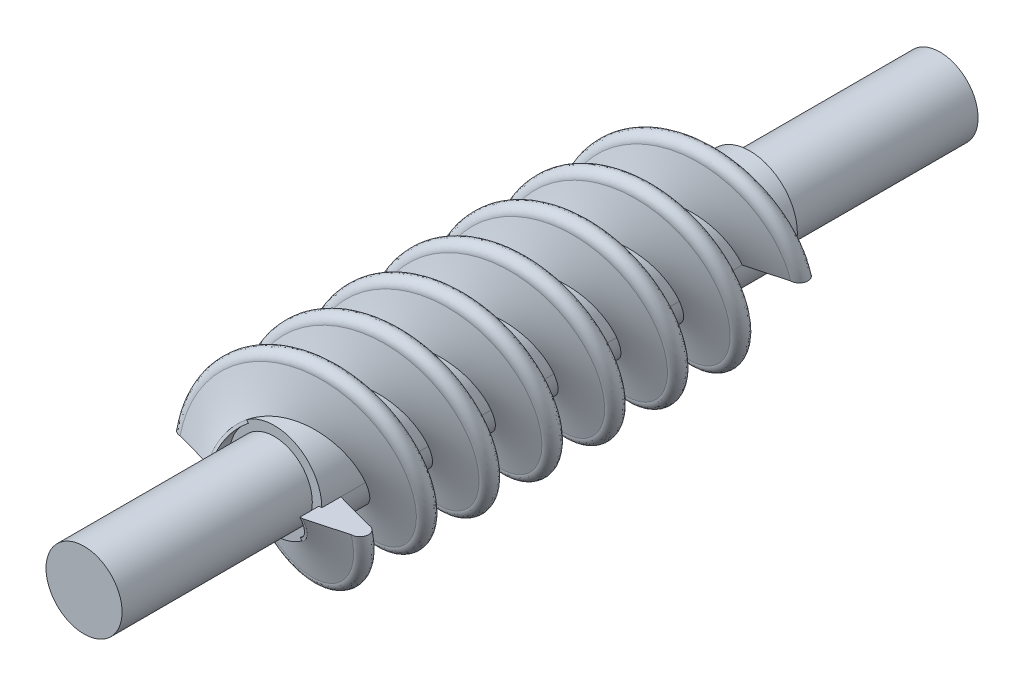
SolidWorks part; units mm, degrees
ref_plane "Plan de face" through (0, 0, 0) normal (0, 0, 1) x (1, 0, 0)
ref_plane "Plan de dessus" through (0, 0, 0) normal (0, 1, 0) x (1, 0, 0)
ref_plane "Plan de droite" through (0, 0, 0) normal (1, 0, 0) x (0, 0, -1)
sketch "Esquisse1" plane through (0, 0, 0) normal (0, 0, 1) x (1, 0, 0)
  circle A0 centre (0, 0) radius 5
  dimension "D1" = 10
extrude "Boss.-Extru.1" add sketch "Esquisse1" along normal blind 50
sketch "Esquisse3" plane through (0, 0, 50) normal (0, 0, 1) x (1, 0, 0)
  circle A0 centre (0, 0) radius 5
curve "Hélice/Spirale1" pitch 13.2 height 46.2 radius 5 centre (0, 0, 50) axis (0, 0, -1) start towards (-1, 0, 0)
sketch "Esquisse4" plane through (0, 0, 0) normal (0, 1, 0) x (1, 0, 0)
  line L0 (-5, -50) -> (-9, -50) construction
  line L1 (-5, 0) -> (-5, -50) construction
  line L2 (-9, -49.1) -> (-5, -48)
  line L3 (-9, -50.9) -> (-5, -52)
  line L5 (-5, -48) -> (-4.702, -48)
  line L6 (-4.702, -48) -> (-4.702, -52)
  line L7 (-4.702, -52) -> (-5, -52)
  arc A1 (-9, -49.1) -> (-9, -50.9) centre (-9, -50) ccw
  spline S0 degree 3 poles (-5, -50) (-5, -49.7265) (-4.7397, -49.1743) (-3.6276, -48.3502) (-1.9632, -47.525) (0, -46.7) (1.9632, -45.875) (3.6276, -45.05) (4.7397, -44.225) (5.1302, -43.4) (4.7397, -42.575) (3.6276, -41.75) (1.4084, -40.65) (-1.4084, -39.55) (-3.6276, -38.45) (-4.7397, -37.625) (-5.1302, -36.8) (-4.7397, -35.975) (-3.6276, -35.15) (-1.4084, -34.05) (1.4084, -32.95) (3.6276, -31.85) (4.7397, -31.025) (5.1302, -30.2) (4.7397, -29.375) (3.6276, -28.55) (1.4084, -27.45) (-1.4084, -26.35) (-3.6276, -25.25) (-4.7397, -24.425) (-5.1302, -23.6) (-4.7397, -22.775) (-3.6276, -21.95) (-1.4084, -20.85) (1.4084, -19.75) (3.6276, -18.65) (4.7397, -17.825) (5.1302, -17) (4.7397, -16.175) (3.6276, -15.35) (1.4084, -14.25) (-1.4084, -13.15) (-3.6276, -12.05) (-4.7397, -11.225) (-5.1302, -10.4) (-4.7397, -9.575) (-3.6276, -8.75) (-1.9632, -7.925) (0, -7.1) (1.9632, -6.275) (3.6276, -5.4498) (4.7397, -4.6257) (5, -4.0735) (5, -3.8) knots 0 0 0 0 0.017857 0.035714 0.053571 0.071429 0.089286 0.107143 0.125 0.142857 0.160714 0.178571 0.196429 0.232143 0.25 0.267857 0.285714 0.303571 0.321429 0.339286 0.375 0.392857 0.410714 0.428571 0.446429 0.464286 0.482143 0.517857 0.535714 0.553571 0.571429 0.589286 0.607143 0.625 0.660714 0.678571 0.696429 0.714286 0.732143 0.75 0.767857 0.803571 0.821429 0.839286 0.857143 0.875 0.892857 0.910714 0.928571 0.946429 0.964286 0.982143 1 1 1 1 construction
  dimension "D3" = 0.9
  dimension "D1" = 4
  dimension "D2" = 4
sweep "Balayage2" add profiles "Esquisse4" path "Hélice/Spirale1"
pattern_circular "CirPattern1" count 2 over 360 about axis through (0, 0, 50) along (0, 0, -1) of "Balayage2"
sketch "arbre" plane through (0, 0, 0) normal (0, 0, -1) x (-1, 0, 0)
  circle A0 centre (0, 0) radius 4
  dimension "D1" = 8
extrude "Boss.-Extru.3" add sketch "arbre" along normal blind 20 and the other way blind 70
